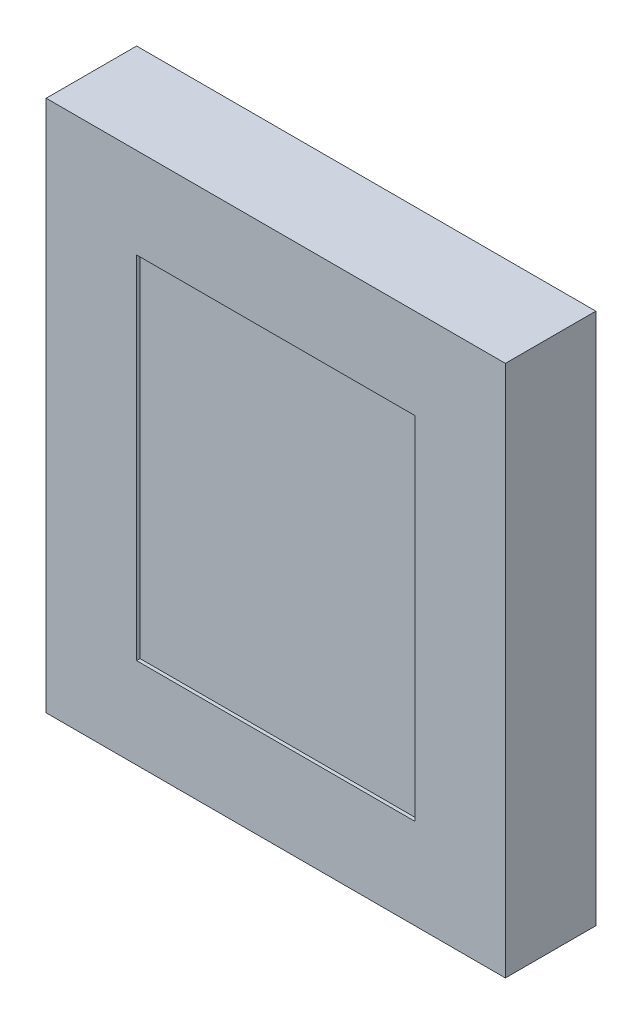
SolidWorks part; units mm, degrees
ref_plane "Plano frontal" through (0, 0, 0) normal (0, 0, 1) x (1, 0, 0)
ref_plane "Plano superior" through (0, 0, 0) normal (0, 1, 0) x (1, 0, 0)
ref_plane "Plano direito" through (0, 0, 0) normal (1, 0, 0) x (0, 0, -1)
sketch "Esboço1" plane through (0, 0, 0) normal (0, 0, 1) x (1, 0, 0)
  line L1 (200, 252.5) -> (-200, 252.5)
  line L2 (200, 252.5) -> (200, -252.5)
  line L3 (200, -252.5) -> (-200, -252.5)
  line L4 (-200, 252.5) -> (-200, -252.5)
  line L5 (200, 252.5) -> (-200, -252.5) construction
  line L6 (200, -252.5) -> (-200, 252.5) construction
  point P0 (0, 0)
  dimension "D1" = 505
  dimension "D2" = 400
extrude "Ressalto-extrusão1" add sketch "Esboço1" along normal blind 60 and the other way blind 60
sketch "Esboço2" plane through (0, 0, 0) normal (0, 0, 1) x (1, 0, 0)
  line L4 (-200, 252.5) -> (-200, -252.5)
  line L5 (-200, -252.5) -> (200, -252.5)
  line L6 (200, -252.5) -> (200, 252.5)
  line L7 (200, 252.5) -> (-200, 252.5)
  line L8 (-200, 252.5) -> (-200, -252.5)
  line L9 (-200, -252.5) -> (200, -252.5)
  line L10 (200, -252.5) -> (200, 252.5)
  line L11 (200, 252.5) -> (-200, 252.5)
  line L16 (-330, 382.5) -> (-330, -382.5)
  line L17 (-330, -382.5) -> (330, -382.5)
  line L18 (330, -382.5) -> (330, 382.5)
  line L19 (330, 382.5) -> (-330, 382.5)
  line L20 (-330, 382.5) -> (-330, -382.5)
  line L21 (-330, -382.5) -> (330, -382.5)
  line L22 (330, -382.5) -> (330, 382.5)
  line L23 (330, 382.5) -> (-330, 382.5)
  dimension "D1" = 0
  dimension "D2" = 130
extrude "Ressalto-extrusão2" add sketch "Esboço2" along normal blind 65 and the other way blind 65 separate body
